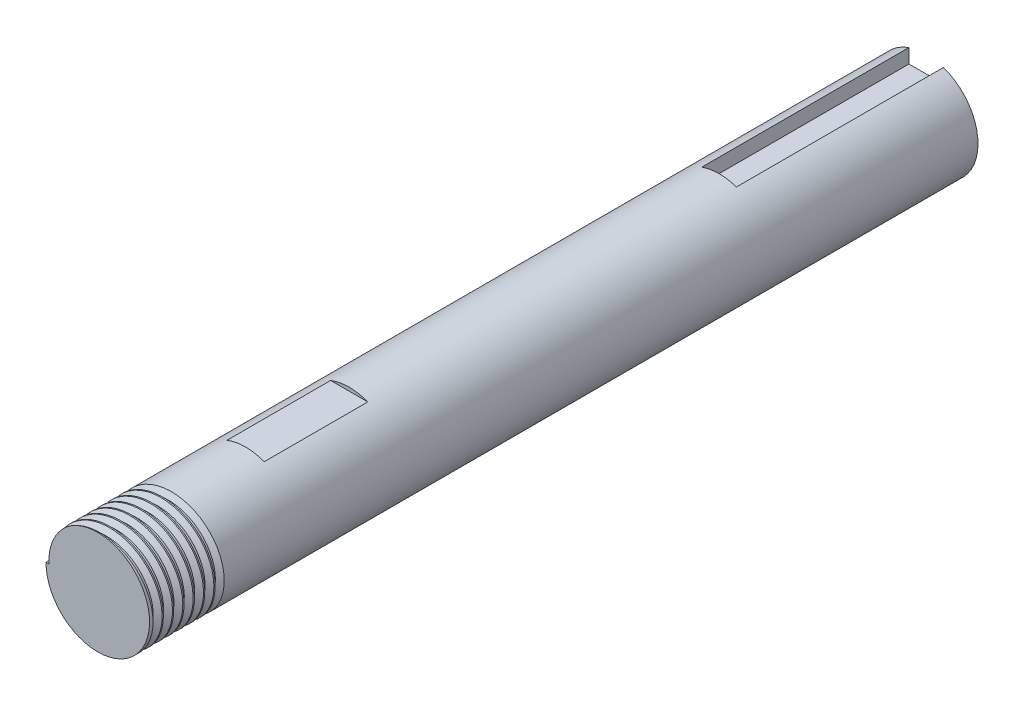
SolidWorks part; units mm, degrees
ref_plane "Front Plane" through (0, 0, 0) normal (0, 0, 1) x (1, 0, 0)
ref_plane "Top Plane" through (0, 0, 0) normal (0, 1, 0) x (1, 0, 0)
ref_plane "Right Plane" through (0, 0, 0) normal (1, 0, 0) x (0, 0, -1)
sketch "Sketch1" plane through (0, 0, 0) normal (0, 0, 1) x (1, 0, 0)
  circle A0 centre (0, 0) radius 7.5
  dimension "D1" = 15
extrude "Boss-Extrude1" add sketch "Sketch1" along normal mid plane 120
thread "Thread1" pitch 1.5 method cut profile "Thread Profile1" start angle 0, offset 0.25, length 10, pitch 1.5, diameter 15
ref_plane "Plane1" through (-7.5, 0, 60.25) normal (0, -1, 0) x (-1, 0, 0)
sketch "Thread Profile1" plane through (-7.5, 0, 60.25) normal (0, -1, 0) x (-1, 0, 0)
  line L0 (0, 0) -> (0, 1.5) construction
  line L11 (0, 0) -> (0, 1.3125)
  line L12 (0, 1.3125) -> (-0.8119, 0.8437)
  line L13 (-0.8119, 0.8437) -> (-0.8119, 0.4687)
  line L15 (-0.8119, 0.4687) -> (0, 0)
  line L17 (-0.8119, 0.6562) -> (0, 0.6562) construction
  point P2 (0, 0)
  dimension "Pitch" = 1.5
  dimension "Profile_Angle" = 60
  dimension "Profile_Land" = 0.375
  dimension "Profile_Height" = 0.8119
sketch "Sketch2" plane through (0, 0, -60) normal (0, 0, -1) x (-1, 0, 0)
  line L1 (-2.5, 10) -> (2.5, 10)
  line L2 (-2.5, 10) -> (-2.5, 5)
  line L3 (-2.5, 5) -> (2.5, 5)
  line L4 (2.5, 10) -> (2.5, 5)
  line L5 (-2.5, 10) -> (2.5, 5) construction
  line L6 (-2.5, 5) -> (2.5, 10) construction
  circle A0 centre (0, 0) radius 7.5 construction
  point P0 (0, 7.5)
extrude "Cut-Extrude1" cut sketch "Sketch2" against normal blind 30
ref_plane "Plane2" through (0, 0, 38.58) normal (0, 0, 1) x (1, 0, 0)
sketch "Sketch3" plane through (0, 0, 38.58) normal (0, 0, 1) x (1, 0, 0)
  line L1 (-18.076, 13.4576) -> (18.076, 13.4576)
  line L2 (-18.076, 13.4576) -> (-18.076, 7)
  line L3 (-18.076, 7) -> (18.076, 7)
  line L4 (18.076, 13.4576) -> (18.076, 7)
  line L5 (-18.076, 13.4576) -> (18.076, 7) construction
  line L6 (-18.076, 7) -> (18.076, 13.4576) construction
  point P0 (0, 10.2288)
  point P5 (0, 7)
  dimension "D1" = 7
extrude "Cut-Extrude2" cut sketch "Sketch3" against normal blind 15
